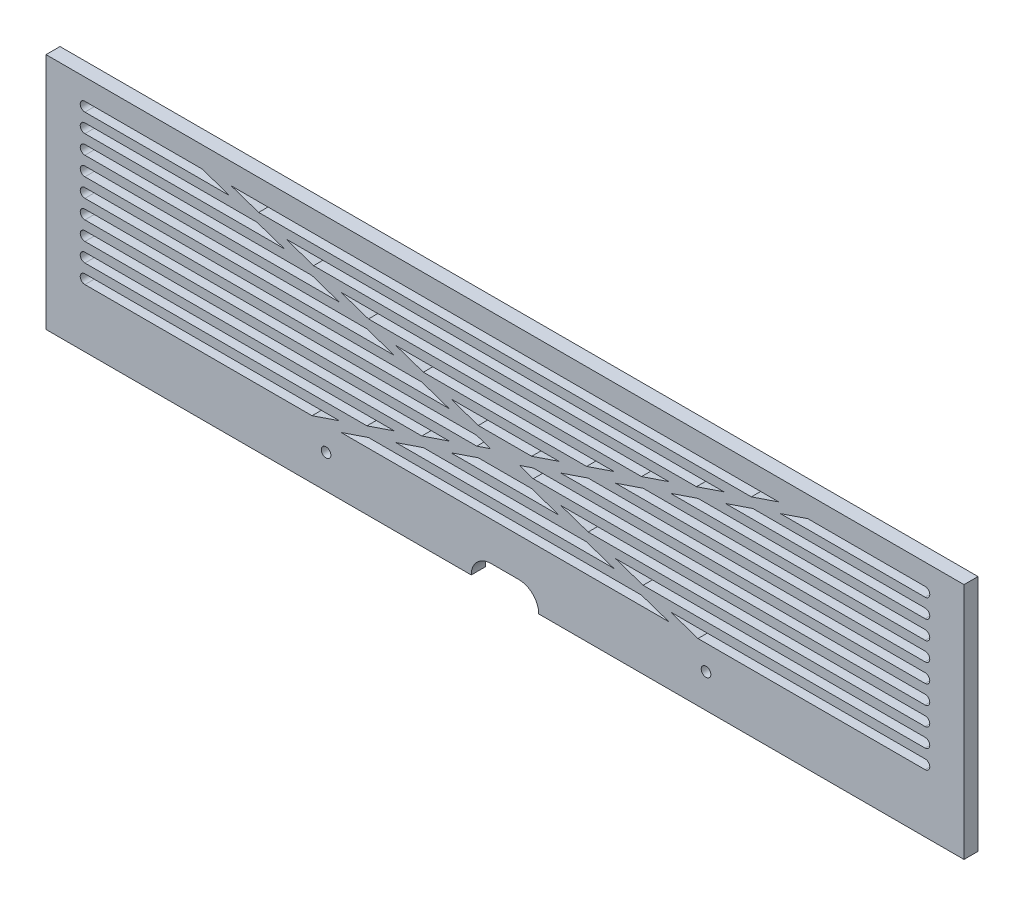
SolidWorks part; units mm, degrees
ref_plane "Front Plane" through (0, 0, 0) normal (0, 0, 1) x (1, 0, 0)
ref_plane "Top Plane" through (0, 0, 0) normal (0, 1, 0) x (1, 0, 0)
ref_plane "Right Plane" through (0, 0, 0) normal (1, 0, 0) x (0, 0, -1)
sketch "Sketch1" plane through (0, 0, 0) normal (0, 0, 1) x (1, 0, 0)
  line L1 (147.5, -38.25) -> (-147.5, -38.25)
  line L2 (147.5, -38.25) -> (147.5, 38.25)
  line L3 (147.5, 38.25) -> (-147.5, 38.25)
  line L4 (-147.5, -38.25) -> (-147.5, 38.25)
  line L5 (147.5, -38.25) -> (-147.5, 38.25) construction
  line L6 (147.5, 38.25) -> (-147.5, -38.25) construction
  point P0 (0, 0)
  dimension "D1" = 295
  dimension "D2" = 76.5
extrude "Boss-Extrude1" add sketch "Sketch1" along normal blind 4.5 contours L3 L4 L1 L2
sketch "Sketch2" plane through (0, 0, 4.5) normal (0, 0, 1) x (1, 0, 0)
  line L0 (147.5, 38.25) -> (138, 28.75) construction
  line L1 (147.5, 38.25) -> (138, 38.25) construction
  line L2 (147.5, 38.25) -> (147.5, 28.75) construction
  line L3 (147.5, 28.75) -> (138, 28.75) construction
  line L4 (138, 38.25) -> (138, 28.75) construction
  line L5 (0, 0) -> (0, -38.25) construction
  line L6 (-147.5, 38.25) -> (-138, 38.25) construction
  line L7 (-147.5, 38.25) -> (-147.5, 28.75) construction
  line L8 (-147.5, 28.75) -> (-138, 28.75) construction
  line L9 (-138, 38.25) -> (-138, 28.75) construction
  line L10 (147.5, -38.25) -> (-147.5, -38.25) construction
  line L11 (4.4678, -38.25) -> (-4.4678, -38.25) construction
  line L12 (4.4678, -44.6294) -> (-4.4678, -44.6294)
  line L13 (4.4678, -31.8706) -> (-4.4678, -31.8706)
  line L15 (-147.5, -38.25) -> (-138, -38.25) construction
  line L16 (-147.5, -38.25) -> (-147.5, -33.25) construction
  line L17 (-147.5, -33.25) -> (-138, -33.25) construction
  line L18 (-138, -38.25) -> (-138, -33.25) construction
  line L19 (147.5, -38.25) -> (138, -38.25) construction
  line L20 (147.5, -38.25) -> (147.5, -33.25) construction
  line L21 (147.5, -33.25) -> (138, -33.25) construction
  line L22 (138, -38.25) -> (138, -33.25) construction
  circle A0 centre (138, 28.75) radius 1.5 construction
  circle A1 centre (-138, 28.75) radius 1.5 construction
  arc A2 (4.4678, -44.6294) -> (4.4678, -31.8706) centre (4.4678, -38.25) ccw
  arc A3 (-4.4678, -31.8706) -> (-4.4678, -44.6294) centre (-4.4678, -38.25) ccw
  circle A4 centre (-138, -33.25) radius 1.5 construction
  circle A5 centre (138, -33.25) radius 1.5 construction
  point P19 (0, -38.25)
  dimension "D3" = 9.5
  dimension "D5" = 9.5
  dimension "D7" = 9.5
  dimension "D1" = 9.5
  dimension "D2" = 9.5
  dimension "D4" = 9.5
  dimension "D6" = 5
  dimension "D8" = 5
extrude "Cut-Extrude1" cut sketch "Sketch2" against normal up to next
sketch "Sketch3" plane through (0, 0, 4.5) normal (0, 0, 1) x (1, 0, 0)
  line L0 (147.5, -38.25) -> (64.6, -38.25) construction
  line L1 (147.5, -38.25) -> (10.8472, -38.25) construction
  line L2 (64.6, -38.25) -> (64.6, -27.45) construction
  line L3 (64.6, -27.45) -> (-57.5, -27.45) construction
  circle A0 centre (64.6, -27.45) radius 1.55
  circle A1 centre (-57.5, -27.45) radius 1.55
extrude "Cut-Extrude2" cut sketch "Sketch3" against normal blind 14
sketch "Sketch4" plane through (0, 0, 4.5) normal (0, 0, 1) x (1, 0, 0)
  line L0 (147.5, 38.25) -> (52.5, 38.25) construction
  line L1 (147.5, 38.25) -> (-147.5, 38.25) construction
  line L2 (52.5, 38.25) -> (52.5, 15.25) construction
  line L3 (57.5, 15.25) -> (47.5, 15.25) construction
  line L4 (57.5, 14.4) -> (47.5, 14.4)
  line L5 (57.5, 16.1) -> (47.5, 16.1)
  line L6 (57.5, 19.25) -> (47.5, 19.25) construction
  line L7 (57.5, 18.4) -> (47.5, 18.4)
  line L8 (57.5, 20.1) -> (47.5, 20.1)
  arc A0 (57.5, 14.4) -> (57.5, 16.1) centre (57.5, 15.25) ccw
  arc A1 (47.5, 16.1) -> (47.5, 14.4) centre (47.5, 15.25) ccw
  arc A2 (57.5, 18.4) -> (57.5, 20.1) centre (57.5, 19.25) ccw
  arc A3 (47.5, 20.1) -> (47.5, 18.4) centre (47.5, 19.25) ccw
  point P8 (52.5, 15.25)
  point P16 (52.5, 19.25)
  dimension "D3" = 2
  dimension "D1" = 95
  dimension "D2" = 23
extrude "Cut-Extrude3" [suppressed] cut sketch "Sketch4" against normal blind 8
sketch "Sketch5" plane through (0, 0, 4.5) normal (0, 0, 1) x (1, 0, 0)
  line L0 (0, 38.25) -> (0, -31.8706) construction
  line L1 (147.5, 38.25) -> (-147.5, 38.25) construction
  line L2 (4.4678, -31.8706) -> (-4.4678, -31.8706) construction
  line L3 (135, 24) -> (-135, 24) construction
  line L4 (135, 30) -> (-135, 30) construction
  line L5 (135, 28.5) -> (-135, 28.5)
  line L6 (135, 31.5) -> (-135, 31.5)
  line L7 (135, 22.5) -> (-135, 22.5)
  line L8 (135, 25.5) -> (-135, 25.5)
  line L9 (135, 18) -> (-135, 18) construction
  line L10 (135, 16.5) -> (-135, 16.5)
  line L11 (135, 19.5) -> (-135, 19.5)
  line L12 (135, 12) -> (-135, 12) construction
  line L13 (135, 10.5) -> (-135, 10.5)
  line L14 (135, 13.5) -> (-135, 13.5)
  line L15 (135, 6) -> (-135, 6) construction
  line L16 (135, 4.5) -> (-135, 4.5)
  line L17 (135, 7.5) -> (-135, 7.5)
  line L18 (135, 0) -> (-135, 0) construction
  line L19 (135, -1.5) -> (-135, -1.5)
  line L20 (135, 1.5) -> (-135, 1.5)
  line L21 (135, -6) -> (-135, -6) construction
  line L22 (135, -7.5) -> (-135, -7.5)
  line L23 (135, -4.5) -> (-135, -4.5)
  line L24 (135, -12) -> (-135, -12) construction
  line L25 (135, -13.5) -> (-135, -13.5)
  line L26 (135, -10.5) -> (-135, -10.5)
  line L27 (135, -18) -> (-135, -18) construction
  line L28 (135, -19.5) -> (-135, -19.5)
  line L29 (135, -16.5) -> (-135, -16.5)
  arc A0 (135, 28.5) -> (135, 31.5) centre (135, 30) ccw
  arc A1 (-135, 31.5) -> (-135, 28.5) centre (-135, 30) ccw
  arc A2 (135, 22.5) -> (135, 25.5) centre (135, 24) ccw
  arc A3 (-135, 25.5) -> (-135, 22.5) centre (-135, 24) ccw
  arc A4 (135, 16.5) -> (135, 19.5) centre (135, 18) ccw
  arc A5 (-135, 19.5) -> (-135, 16.5) centre (-135, 18) ccw
  arc A6 (135, 10.5) -> (135, 13.5) centre (135, 12) ccw
  arc A7 (-135, 13.5) -> (-135, 10.5) centre (-135, 12) ccw
  arc A8 (135, 4.5) -> (135, 7.5) centre (135, 6) ccw
  arc A9 (-135, 7.5) -> (-135, 4.5) centre (-135, 6) ccw
  arc A10 (135, -1.5) -> (135, 1.5) centre (135, 0) ccw
  arc A11 (-135, 1.5) -> (-135, -1.5) centre (-135, 0) ccw
  arc A12 (135, -7.5) -> (135, -4.5) centre (135, -6) ccw
  arc A13 (-135, -4.5) -> (-135, -7.5) centre (-135, -6) ccw
  arc A14 (135, -13.5) -> (135, -10.5) centre (135, -12) ccw
  arc A15 (-135, -10.5) -> (-135, -13.5) centre (-135, -12) ccw
  arc A16 (135, -19.5) -> (135, -16.5) centre (135, -18) ccw
  arc A17 (-135, -16.5) -> (-135, -19.5) centre (-135, -18) ccw
  point P10 (0, 30)
  point P17 (0, 24)
  point P24 (0, 18)
  point P31 (0, 12)
  point P38 (0, 6)
  point P45 (0, 0)
  point P52 (0, -6)
  point P59 (0, -12)
  point P64 (0, -18)
  dimension "D1" = 270
  dimension "D2" = 1.5
  dimension "D3" = 9
extrude "Cut-Extrude4" cut sketch "Sketch5" against normal through all
sketch "Sketch6" plane through (0, 0, 4.5) normal (0, 0, 1) x (1, 0, 0)
  line L0 (0, 0) -> (0, 34) construction
  line L1 (0, 34) -> (-100, 34) construction
  line L2 (-100, 34) -> (100, 34) construction
  line L3 (-100, -34) -> (100, 34) construction
  line L4 (-100.4829, -32.5798) -> (99.5171, 35.4202)
  line L5 (-99.5171, -35.4202) -> (100.4829, 32.5798)
  line L6 (100, -34) -> (-100, 34) construction
  line L7 (99.5171, -35.4202) -> (-100.4829, 32.5798)
  line L8 (100.4829, -32.5798) -> (-99.5171, 35.4202)
  arc A0 (-100.4829, -32.5798) -> (-99.5171, -35.4202) centre (-100, -34) ccw
  arc A1 (100.4829, 32.5798) -> (99.5171, 35.4202) centre (100, 34) ccw
  arc A2 (99.5171, -35.4202) -> (100.4829, -32.5798) centre (100, -34) ccw
  arc A3 (-99.5171, 35.4202) -> (-100.4829, 32.5798) centre (-100, 34) ccw
  point P6 (0, 0)
  point P12 (0, 0)
extrude "Boss-Extrude2" add sketch "Sketch6" against normal blind 4.5 contours L4 A1 L5 A0 | L7 A3 L8 A2
